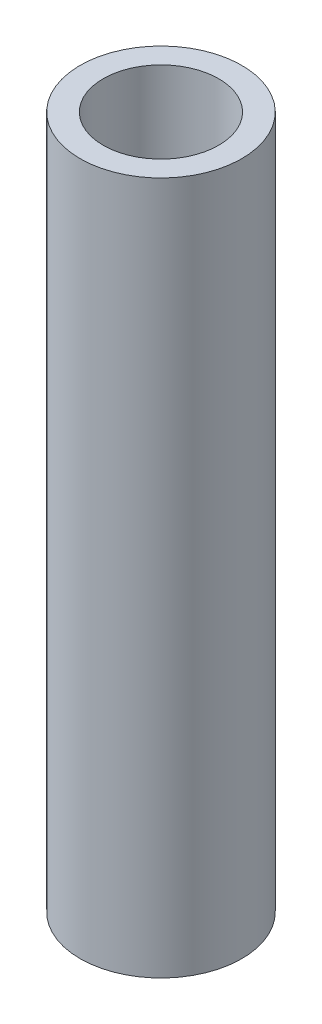
SolidWorks part; units mm, degrees
material "Silicon"
ref_plane "Front Plane" through (0, 0, 0) normal (0, 0, 1) x (1, 0, 0)
ref_plane "Top Plane" through (0, 0, 0) normal (0, 1, 0) x (1, 0, 0)
ref_plane "Right Plane" through (0, 0, 0) normal (1, 0, 0) x (0, 0, -1)
sketch "Sketch1" plane through (0, 0, 0) normal (0, 1, 0) x (1, 0, 0)
  circle A0 centre (0, 0) radius 31.75
  circle A1 centre (0, 0) radius 44.45
  dimension "D1" = 88.9
  dimension "D2" = 12.7
extrude "Boss-Extrude1" add sketch "Sketch1" along normal blind 381
